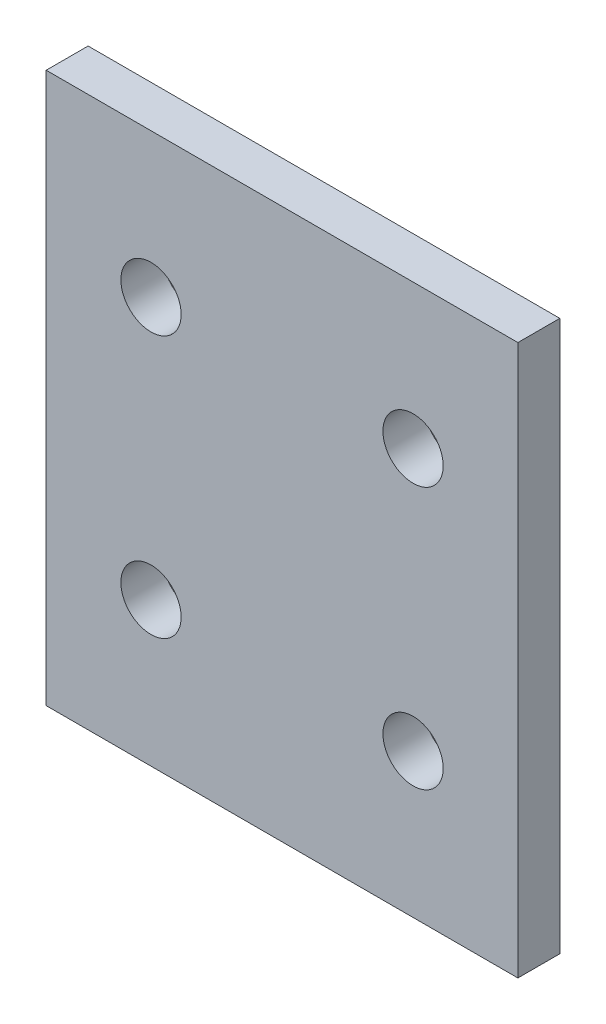
SolidWorks part; units mm, degrees
material "Простая углеродистая сталь"
ref_plane "Спереди" through (0, 0, 0) normal (0, 0, 1) x (1, 0, 0)
ref_plane "Сверху" through (0, 0, 0) normal (0, 1, 0) x (1, 0, 0)
ref_plane "Справа" through (0, 0, 0) normal (1, 0, 0) x (0, 0, -1)
sketch "Эскиз1" plane through (0, 0, 0) normal (0, 0, 1) x (1, 0, 0)
  line L0 (90, 0) -> (90, -210) construction
  line L1 (0, 0) -> (180, 0)
  line L2 (0, 0) -> (0, -210)
  line L3 (0, -210) -> (180, -210)
  line L4 (180, 0) -> (180, -210)
  line L5 (0, -105) -> (180, -105) construction
  circle A0 centre (40, -55) radius 11.5
  circle A1 centre (140, -55) radius 11.5
  circle A2 centre (140, -155) radius 11.5
  circle A3 centre (40, -155) radius 11.5
  dimension "D3" = 23
  dimension "D4" = 100
  dimension "D5" = 100
  dimension "D1" = 180
  dimension "D2" = 210
base flange "Базовая кромка1" sketch "Эскиз1" thickness 16 reverse thickness direction no parameters "D1"=3
sketch "Сгиб-Линии1" [suppressed] plane through (0, 0, 0) normal (0, 1, 0) x (1, 0, 0)
sketch "Граничная рамка1" [suppressed] plane through (0, 0, 0) normal (0, 1, 0) x (1, 0, 0)
sheet metal parameters "Листовой металл1" thickness 16 parameters "D1"=3
flat pattern "Развертка1" [suppressed]
sketch "Сгиб-Линии2" plane through (0, 0, 0) normal (0, 1, 0) x (1, 0, 0)
sketch3d "Граничная рамка2" [suppressed]
  line L0 (180, 0, 0) -> (180, -210, 0) construction
  line L1 (0, 0, 0) -> (0, -210, 0) construction
  line L2 (180, 0, 0) -> (0, 0, 0) construction
  line L3 (180, -210, 0) -> (0, -210, 0) construction
